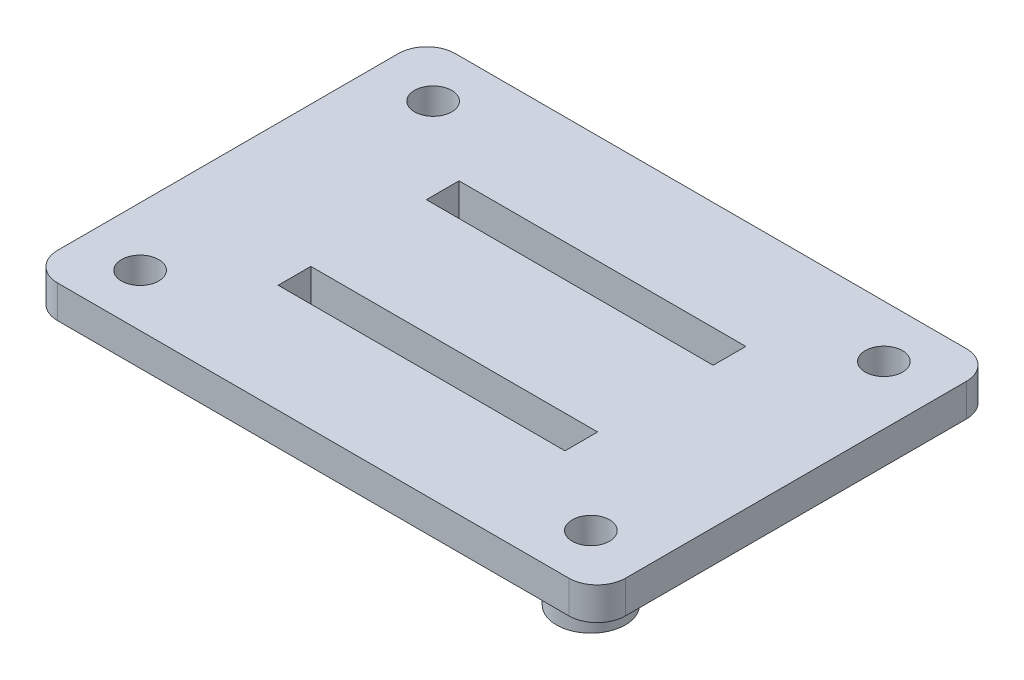
SolidWorks part; units mm, degrees
ref_plane "前视基准面" through (0, 0, 0) normal (0, 0, 1) x (1, 0, 0)
ref_plane "上视基准面" through (0, 0, 0) normal (0, 1, 0) x (1, 0, 0)
ref_plane "右视基准面" through (0, 0, 0) normal (1, 0, 0) x (0, 0, -1)
other "Configuration Table"
sketch "草图1" plane through (0, 0, 0) normal (0, 1, 0) x (1, 0, 0)
  line L0 (-89.3251, 0) -> (102.0425, 0) construction
  line L1 (0, 56.7239) -> (0, -62.578) construction
  line L2 (-20.2, -8.1375) -> (20.2, -8.1375)
  line L3 (-20.2, 12.7375) -> (20.2, 12.7375)
  line L4 (-20.2, 12.7375) -> (-20.2, 8.1375)
  line L5 (-20.2, 8.1375) -> (20.2, 8.1375)
  line L6 (20.2, 12.7375) -> (20.2, 8.1375)
  line L7 (-20.2, 12.7375) -> (20.2, 8.1375) construction
  line L8 (-20.2, 8.1375) -> (20.2, 12.7375) construction
  line L9 (20.2, -12.7375) -> (20.2, -8.1375)
  line L10 (-20.2, -12.7375) -> (20.2, -12.7375)
  line L11 (-20.2, -12.7375) -> (-20.2, -8.1375)
  circle A0 centre (-31.75, 20.6375) radius 2.625
  circle A4 centre (31.75, 20.6375) radius 2.625
  circle A5 centre (31.75, -20.6375) radius 2.625
  circle A6 centre (-31.75, -20.6375) radius 2.625
  point P13 (0, 10.4375)
  dimension "D5" = 5.25
  dimension "D9" = 5.25
  dimension "D7" = 10.4375
  dimension "D1" = 40.4
  dimension "D2" = 31.75
  dimension "D3" = 4.6
  dimension "D4" = 20.6375
  dimension "D8" = 4.6
  dimension "D10" = 40.4
  dimension "D11" = 7.9
  dimension "D12" = 31.75
sketch "草图3" plane through (0, 0, 0) normal (0, 1, 0) x (1, 0, 0)
  line L1 (-40, -28) -> (40, -28)
  line L2 (-40, -28) -> (-40, 28)
  line L3 (-40, 28) -> (40, 28)
  line L4 (40, -28) -> (40, 28)
  line L5 (-40, -28) -> (40, 28) construction
  line L6 (-40, 28) -> (40, -28) construction
  point P0 (0, 0)
  dimension "D1" = 56
  dimension "D2" = 80
extrude "凸台-拉伸1" add sketch "草图3" along normal blind 4.6
extrude "切除-拉伸1" cut sketch "草图1" along normal up to surface (4.6 mm away) up to face at (0, 4.6, 0)
sketch "草图5" plane through (0, 0, 0) normal (0, -1, 0) x (1, 0, 0)
  circle A0 centre (31.75, 20.6375) radius 4.85
  dimension "D1" = 9.7
extrude "凸台-拉伸2" add sketch "草图5" along normal blind 4.5
sketch "草图7" plane through (0, 4.6, 0) normal (0, 1, 0) x (1, 0, 0)
  line L0 (40, -28) -> (40, 28) construction
  line L1 (31.75, 20.6375) -> (50, 20.6375)
  line L2 (31.75, 20.6375) -> (31.75, -28.0079)
  line L3 (31.75, -28.0079) -> (50, -28.0079)
  line L4 (50, 20.6375) -> (50, -28.0079)
  dimension "D1" = 10
fillet "圆角2" radius 4 4 edges at (-40, 2.3, -28) (40, 2.3, -28) (40, 2.3, 28) (-40, 2.3, 28)
